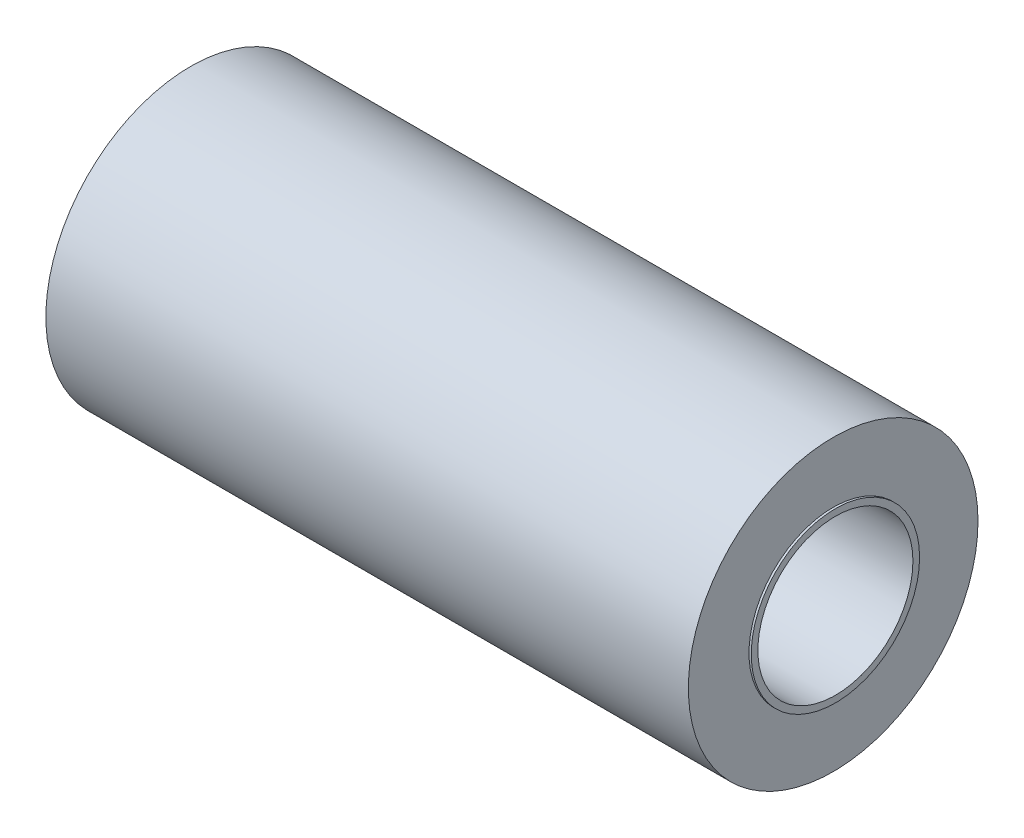
SolidWorks part; units mm, degrees
ref_plane "Alzado" through (0, 0, 0) normal (0, 0, 1) x (1, 0, 0)
ref_plane "Planta" through (0, 0, 0) normal (0, 1, 0) x (1, 0, 0)
ref_plane "Vista lateral" through (0, 0, 0) normal (1, 0, 0) x (0, 0, -1)
sketch "Croquis1" plane through (0, 0, 0) normal (1, 0, 0) x (0, 0, -1)
  circle A0 centre (0, 0) radius 38
  circle A1 centre (0, 0) radius 35
  dimension "D1" = 76
  dimension "D2" = 70
extrude "Saliente-Extruir1" add sketch "Croquis1" along normal blind 146 and the other way blind 146
sketch "Croquis2" plane through (0, 0, 0) normal (1, 0, 0) x (0, 0, -1)
  circle A0 centre (0, 0) radius 65.3639
  circle A1 centre (0, 0) radius 38 construction
  circle A2 centre (0, 0) radius 38
extrude "Saliente-Extruir2" add sketch "Croquis2" along normal blind 145 and the other way blind 145
